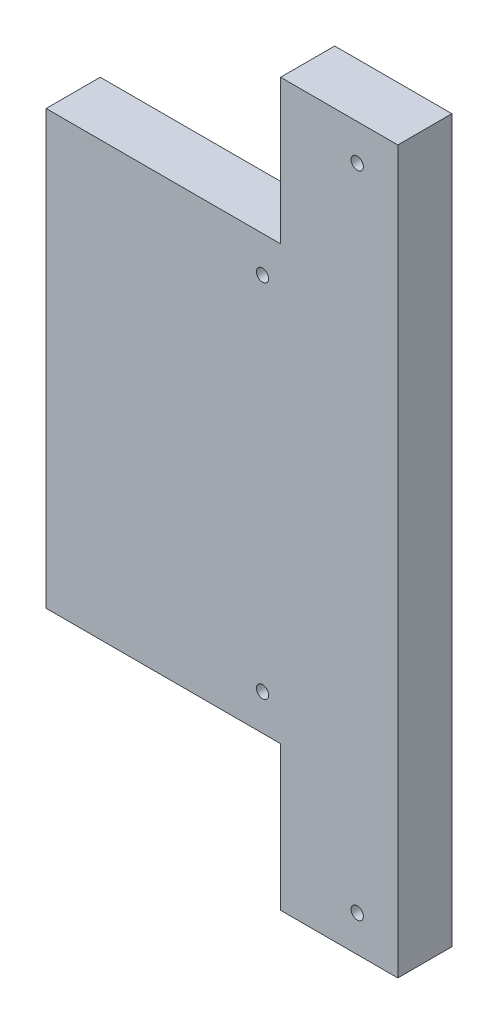
SolidWorks part; units mm, degrees
ref_plane "Front Plane" through (0, 0, 0) normal (1, 0, 0) x (0, 1, 0)
ref_plane "Top Plane" through (0, 0, 0) normal (0, 0, 1) x (0, 1, 0)
ref_plane "Right Plane" through (0, 0, 0) normal (0, 1, 0) x (-1, 0, 0)
sketch "Sketch1" plane through (0, 0, 0) normal (0, 0, 1) x (0, 1, 0)
  line L0 (-100, 11.25) -> (-100, 21.25)
  line L1 (100, -11.25) -> (-100, -11.25)
  line L2 (100, -11.25) -> (100, 11.25)
  line L3 (100, 11.25) -> (-100, 11.25) construction
  line L4 (-100, -11.25) -> (-100, 11.25)
  line L5 (100, -11.25) -> (-100, 11.25) construction
  line L6 (100, 11.25) -> (-100, -11.25) construction
  line L7 (100, 11.25) -> (100, 21.25)
  line L8 (-100, 21.25) -> (100, 21.25)
  point P0 (0, 0)
  dimension "D1" = 200
  dimension "D2" = 22.5
  dimension "D3" = 10
extrude "Boss-Extrude1" add sketch "Sketch1" along normal blind 15
sketch "Sketch2" plane through (0, 0, 15) normal (0, 0, 1) x (1, 0, 0)
  line L0 (0, 50) -> (0, -50) construction
  line L2 (11.5, 72) -> (-11.5, 72)
  line L3 (11.5, 72) -> (11.5, -72)
  line L4 (11.5, -72) -> (-11.5, -72)
  line L5 (-11.5, 72) -> (-11.5, -72)
  line L6 (11.5, 72) -> (-11.5, -72) construction
  line L7 (11.5, -72) -> (-11.5, 72) construction
  circle A0 centre (0, 50) radius 3.15 construction
  circle A1 centre (0, -50) radius 3.15 construction
  point P4 (0, 0)
  point P7 (0, 0)
  dimension "D1" = 6.3
  dimension "D2" = 6.3
  dimension "D5" = 23
  dimension "D3" = 100
  dimension "D4" = 144
sketch "Sketch4" plane through (0, 0, 15) normal (0, 0, 1) x (1, 0, 0)
  line L0 (0, 90) -> (0, -90) construction
  circle A0 centre (0, 90) radius 1.7
  circle A1 centre (0, -90) radius 1.7
  point P4 (0, 0)
  dimension "D1" = 3.4
  dimension "D2" = 3.4
  dimension "D3" = 180
extrude "Cut-Extrude3" cut sketch "Sketch4" against normal blind 15
hole_wizard "CBORE for M3 SBHCS1" positions "3DSketch1" profile "Sketch5" counterbore size "M3" standard "ANSI Metric"
sketch3d "3DSketch1"
  line L0 (0, 90, 0) -> (0, 90, 15) construction
  point P0 (0, 90, 0)
sketch "Sketch5" plane through (0, 90, 0) normal (1, 0, 0) x (0, 1, 0)
  line L0 (0, 0) -> (0, 4.1715)
  line L1 (0, 4.1715) -> (1.7, 3.15)
  line L2 (1.7, 3.15) -> (1.7, 1.65)
  line L3 (1.7, 1.65) -> (3.35, 1.65)
  line L4 (3.35, 1.65) -> (3.35, 0)
  line L5 (3.35, 0) -> (0, 0)
  line L10 (0, 4.1715) -> (-1.7, 3.15) construction
  line L11 (0, -6.35) -> (0, 107.95) construction
  dimension "Hole Dia." = 3.4
  dimension "Hole Depth" = 3.15
  dimension "C'Bore Dia." = 6.7
  dimension "C'Bore Depth" = 1.65
  dimension "Drill Angle" = 118
hole_wizard "CBORE for M3 SBHCS2" positions "3DSketch2" profile "Sketch6" counterbore size "M3" standard "ANSI Metric"
sketch3d "3DSketch2"
  line L0 (0, -90, 0) -> (0, -90, 15) construction
  point P0 (0, -90, 0)
sketch "Sketch6" plane through (0, -90, 0) normal (1, 0, 0) x (0, 1, 0)
  line L0 (0, 0) -> (0, 4.1715)
  line L1 (0, 4.1715) -> (1.7, 3.15)
  line L2 (1.7, 3.15) -> (1.7, 1.65)
  line L3 (1.7, 1.65) -> (3.35, 1.65)
  line L4 (3.35, 1.65) -> (3.35, 0)
  line L5 (3.35, 0) -> (0, 0)
  line L10 (0, 4.1715) -> (-1.7, 3.15) construction
  line L11 (0, -6.35) -> (0, 107.95) construction
  dimension "Hole Dia." = 3.4
  dimension "Hole Depth" = 3.15
  dimension "C'Bore Dia." = 6.7
  dimension "C'Bore Depth" = 1.65
  dimension "Drill Angle" = 118
sketch "Sketch7" plane through (0, 0, 0) normal (0, 0, -1) x (1, 0, 0)
  line L0 (0, 0) -> (-21.25, 0) construction
  line L1 (-21.25, -100) -> (-21.25, 100) construction
  line L2 (-21.25, 60) -> (-21.25, -60)
  line L3 (-21.25, 60) -> (-86.25, 60)
  line L4 (-86.25, 60) -> (-86.25, -60)
  line L5 (-21.25, -60) -> (-86.25, -60)
  point P7 (-21.25, 0)
  dimension "D1" = 65
  dimension "D2" = 120
extrude "Boss-Extrude2" add sketch "Sketch7" against normal blind 15
sketch "Sketch9" plane through (0, 0, 15) normal (0, 0, 1) x (1, 0, 0)
  line L0 (-21.25, -60) -> (-86.25, -60) construction
  line L1 (-21.25, 60) -> (-31.25, 60)
  line L2 (-21.25, 60) -> (-21.25, -60)
  line L3 (-21.25, -60) -> (-31.25, -60)
  line L4 (-31.25, 60) -> (-31.25, -60)
  dimension "D1" = 10
extrude "Boss-Extrude3" add sketch "Sketch9" along normal blind 12
sketch "Sketch10" plane through (0, 0, 27) normal (0, 0, 1) x (1, 0, 0)
  line L1 (-21.25, 60) -> (-86.25, 60)
  line L2 (-21.25, 60) -> (-21.25, -60)
  line L3 (-21.25, -60) -> (-86.25, -60)
  line L4 (-86.25, 60) -> (-86.25, -60)
extrude "Boss-Extrude4" add sketch "Sketch10" along normal blind 7
sketch "Sketch11" plane through (0, 0, 27) normal (0, 0, -1) x (1, 0, 0)
  line L2 (-86.25, 60) -> (-86.25, -60) construction
  line L3 (-86.25, -60) -> (-21.25, -60) construction
  circle A0 centre (-62.74, 0) radius 11
  dimension "D1" = 22
  dimension "D2" = 23.51
  dimension "D3" = 60
extrude "Boss-Extrude5" add sketch "Sketch11" along normal blind 12
sketch "Sketch13" plane through (0, 0, 34) normal (0, 0, 1) x (1, 0, 0)
  line L1 (-21.25, 60) -> (-86.25, 60)
  line L2 (-21.25, 60) -> (-21.25, -60)
  line L3 (-21.25, -60) -> (-86.25, -60)
  line L4 (-86.25, 60) -> (-86.25, -60)
extrude "Cut-Extrude4" cut sketch "Sketch13" against normal blind 19
sketch "Sketch14" plane through (0, 0, 0) normal (0, 0, -1) x (1, 0, 0)
  line L0 (-86.25, -60) -> (-21.25, -60) construction
  line L1 (-21.25, 60) -> (-31.25, 60) construction
  line L2 (-21.25, 60) -> (-21.25, -60) construction
  line L3 (-21.25, -60) -> (-31.25, -60) construction
  line L4 (-31.25, 60) -> (-31.25, -60) construction
  circle A0 centre (-26.25, 50) radius 1.7
  circle A1 centre (-26.25, -50) radius 1.7
  dimension "D2" = 3.4
  dimension "D3" = 3.4
  dimension "D4" = 5
  dimension "D5" = 10
  dimension "D6" = 5
  dimension "D7" = 10
  dimension "D1" = 10
extrude "Cut-Extrude5" cut sketch "Sketch14" against normal blind 15
hole_wizard "CBORE for M3 SBHCS3" positions "3DSketch4" profile "Sketch16" counterbore size "M3" standard "ANSI Metric"
sketch3d "3DSketch4"
  line L0 (-26.25, -50, 15) -> (-26.25, -50, 0) construction
  line L1 (-26.25, 50, 15) -> (-26.25, 50, 0) construction
  point P0 (-26.25, -50, 0)
  point P4 (-26.25, 50, 0)
sketch "Sketch16" plane through (-26.25, -50, 0) normal (1, 0, 0) x (0, 1, 0)
  line L0 (0, 0) -> (0, 4.1715)
  line L1 (0, 4.1715) -> (1.7, 3.15)
  line L2 (1.7, 3.15) -> (1.7, 1.65)
  line L3 (1.7, 1.65) -> (3.35, 1.65)
  line L4 (3.35, 1.65) -> (3.35, 0)
  line L5 (3.35, 0) -> (0, 0)
  line L10 (0, 4.1715) -> (-1.7, 3.15) construction
  line L11 (0, -6.35) -> (0, 107.95) construction
  dimension "Hole Dia." = 3.4
  dimension "Hole Depth" = 3.15
  dimension "C'Bore Dia." = 6.7
  dimension "C'Bore Depth" = 1.65
  dimension "Drill Angle" = 118
